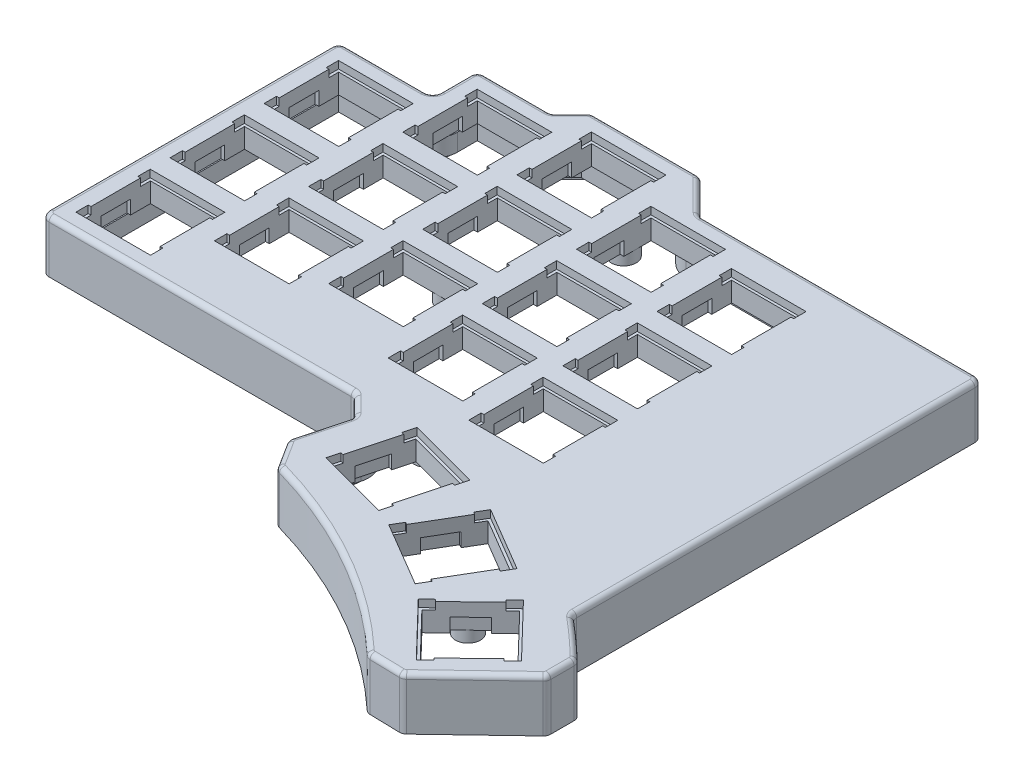
SolidWorks part; units mm, degrees
ref_plane "Piano frontale" through (0, 0, 0) normal (0, 0, 1) x (1, 0, 0)
ref_plane "Piano superiore" through (0, 0, 0) normal (0, 1, 0) x (1, 0, 0)
ref_plane "Piano destro" through (0, 0, 0) normal (1, 0, 0) x (0, 0, -1)
sketch "Schizzo1" plane through (0, 0, 0) normal (0, 1, 0) x (1, 0, 0)
  line L0 (19.05, 28.05) -> (19.05, 9) construction
  line L1 (19.05, 9) -> (19.05, -10.05) construction
  line L2 (38.1, 32.1) -> (38.1, 13.05) construction
  line L3 (38.1, 13.05) -> (38.1, -6) construction
  line L4 (57.15, 25.1) -> (57.15, 6.05) construction
  line L5 (57.15, 6.05) -> (57.15, -13) construction
  line L6 (76.2, 22.35) -> (76.2, 3.3) construction
  line L7 (76.2, 3.3) -> (76.2, -15.75) construction
  line L8 (0, 26.05) -> (0, 30.05) construction
  line L9 (12.05, 35.05) -> (12.05, 39.05) construction
  line L10 (0, 19.05) -> (0, 0) construction
  line L11 (0, 0) -> (0, -19.05) construction
  line L12 (19.05, 22.35) -> (38.1, 22.35) construction
  line L13 (38.1, 22.35) -> (57.15, 22.35) construction
  line L14 (57.15, 22.35) -> (76.2, 22.35) construction
  line L15 (19.05, 22.35) -> (0, 22.35) construction
  line L16 (12.05, 39.05) -> (12.05, 30.05) construction
  line L17 (8.05, 39.05) -> (23.05, 39.05)
  line L18 (23.05, 39.05) -> (27.1, 43.1)
  line L19 (27.1, 43.1) -> (49.1, 43.1)
  line L20 (49.1, 43.1) -> (56.1, 36.1)
  line L21 (56.1, 36.1) -> (113.2, 36.1)
  line L22 (113.2, 36.1) -> (113.2, -46.6839)
  line L23 (-7, -26.05) -> (-7, -30.05) construction
  line L24 (8.05, 39.05) -> (8.05, 30.05)
  line L25 (8.05, 30.05) -> (-11, 30.05)
  line L26 (-11, 30.05) -> (-11, -30.05)
  line L27 (-11, -30.05) -> (52.2495, -30.05)
  line L28 (12.05, 30.05) -> (8.05, 30.05) construction
  line L29 (-7, 19.05) -> (-11, 19.05) construction
  line L30 (45.1, 39.1) -> (45.1, 43.1) construction
  line L31 (31.1, 39.1) -> (27.1, 39.1) construction
  line L32 (27.1, 39.1) -> (27.1, 43.1) construction
  line L33 (45.1, 39.1) -> (49.1, 39.1) construction
  line L34 (49.1, 39.1) -> (49.1, 43.1) construction
  line L35 (57.15, 32.1) -> (57.15, 36.1) construction
  line L36 (27.1, 43.1) -> (27.0899, 42.986) construction
  line L37 (50.1, -113.3763) -> (70.0291, -39) construction
  line L38 (50.1, -113.3763) -> (89.221, -47.0548) construction
  line L39 (50.1, -113.3763) -> (105.5545, -59.9554) construction
  line L40 (52.2495, -49.2894) -> (56.3153, -34.1158)
  line L41 (102.7223, -77.8545) -> (121.3855, -60.0596)
  line L42 (52.2495, -30.05) -> (52.2495, -49.2894)
  line L43 (56.3153, -34.1158) -> (63.57, -36.0597) construction
  line L44 (110.411, -64.9967) -> (113.1713, -67.8917) construction
  line L45 (61.4559, -43.9497) -> (59.2827, -51.1391) construction
  line L46 (56.3153, -34.1158) -> (52.2495, -30.05)
  line L47 (121.3855, -54.0596) -> (121.3855, -60.0596)
  circle A0 centre (50.1, -113.3763) radius 70
  arc A1 (102.7223, -77.8545) -> (52.2495, -49.2894) centre (30.3481, -146.8615) ccw
  arc A2 (121.3855, -54.0596) -> (113.2, -46.6839) centre (30.3481, -146.8615) ccw
  point P0 (19.05, 28.05)
  point P1 (19.05, 9)
  point P2 (19.05, -10.05)
  point P3 (38.1, 32.1)
  point P4 (38.1, 13.05)
  point P5 (38.1, -6)
  point P6 (57.15, 25.1)
  point P7 (57.15, 6.05)
  point P8 (57.15, -13)
  point P9 (76.2, 22.35)
  point P10 (76.2, 3.3)
  point P11 (76.2, -15.75)
  point P23 (0, 19.05)
  point P25 (0, 19.05)
  point P26 (0, -19.05)
  point P43 (76.2, 22.35)
  point P46 (0, 0)
  point P48 (19.05, 28.05)
  point P49 (19.05, 9)
  point P51 (19.05, -10.05)
  point P53 (38.1, 32.1)
  point P54 (38.1, 13.05)
  point P55 (38.1, -6)
  point P59 (57.15, -13)
  point P60 (57.15, 6.05)
  point P61 (57.15, 25.1)
  point P62 (76.2, -15.75)
  point P63 (76.2, 3.3)
  point P69 (50.1, -113.3763)
  point P71 (0, 19.05)
  point P76 (0, -19.05)
  point P80 (105.5545, -59.9554)
  point P86 (89.221, -47.0548)
  point P96 (66.1468, -53.4889)
  line B0 (-7, 26.05) -> (-7, 12.05)
  line B1 (-7, 12.05) -> (7, 12.05)
  line B2 (7, 12.05) -> (7, 26.05)
  line B3 (7, 26.05) -> (-7, 26.05)
  line B4 (0, 26.05) -> (0, 12.05) construction
  line B5 (-7, 19.05) -> (7, 19.05) construction
  line B6 (7.55, 24.075) -> (7.55, 26.575)
  line B7 (-7.55, 26.575) -> (7.55, 26.575)
  line B8 (-7.55, 11.525) -> (7.55, 11.525)
  line B9 (-7, 24.075) -> (-7.55, 24.075)
  line B10 (-7.55, 24.075) -> (-7.55, 26.575)
  line B11 (7, 24.075) -> (7.55, 24.075)
  line B12 (7, 12.05) -> (-7, 12.05)
  line B13 (7, 14.025) -> (7.55, 14.025)
  line B14 (7.55, 14.025) -> (7.55, 11.525)
  line B15 (-7.55, 14.025) -> (-7.55, 11.525)
  line B16 (-7, 14.025) -> (-7.55, 14.025)
  line B17 (-7, 7) -> (-7, -7)
  line B18 (-7, -7) -> (7, -7)
  line B19 (7, -7) -> (7, 7)
  line B20 (7, 7) -> (-7, 7)
  line B21 (0, 7) -> (0, -7) construction
  line B22 (-7, 0) -> (7, 0) construction
  line B23 (7.55, 5.025) -> (7.55, 7.525)
  line B24 (-7.55, 7.525) -> (7.55, 7.525)
  line B25 (-7.55, -7.525) -> (7.55, -7.525)
  line B26 (-7, 5.025) -> (-7.55, 5.025)
  line B27 (-7.55, 5.025) -> (-7.55, 7.525)
  line B28 (7, 5.025) -> (7.55, 5.025)
  line B29 (7, -7) -> (-7, -7)
  line B30 (7, -5.025) -> (7.55, -5.025)
  line B31 (7.55, -5.025) -> (7.55, -7.525)
  line B32 (-7.55, -5.025) -> (-7.55, -7.525)
  line B33 (-7, -5.025) -> (-7.55, -5.025)
  line B34 (12.05, -3.05) -> (12.05, -17.05)
  line B35 (12.05, -17.05) -> (26.05, -17.05)
  line B36 (26.05, -17.05) -> (26.05, -3.05)
  line B37 (26.05, -3.05) -> (12.05, -3.05)
  line B38 (19.05, -3.05) -> (19.05, -17.05) construction
  line B39 (12.05, -10.05) -> (26.05, -10.05) construction
  line B40 (26.6, -5.025) -> (26.6, -2.525)
  line B41 (11.5, -2.525) -> (26.6, -2.525)
  line B42 (11.5, -17.575) -> (26.6, -17.575)
  line B43 (12.05, -5.025) -> (11.5, -5.025)
  line B44 (11.5, -5.025) -> (11.5, -2.525)
  line B45 (26.05, -5.025) -> (26.6, -5.025)
  line B46 (26.05, -17.05) -> (12.05, -17.05)
  line B47 (26.05, -15.075) -> (26.6, -15.075)
  line B48 (26.6, -15.075) -> (26.6, -17.575)
  line B49 (11.5, -15.075) -> (11.5, -17.575)
  line B50 (12.05, -15.075) -> (11.5, -15.075)
  line B51 (12.05, 16) -> (12.05, 2)
  line B52 (12.05, 2) -> (26.05, 2)
  line B53 (26.05, 2) -> (26.05, 16)
  line B54 (26.05, 16) -> (12.05, 16)
  line B55 (19.05, 16) -> (19.05, 2) construction
  line B56 (12.05, 9) -> (26.05, 9) construction
  line B57 (26.6, 14.025) -> (26.6, 16.525)
  line B58 (11.5, 16.525) -> (26.6, 16.525)
  line B59 (11.5, 1.475) -> (26.6, 1.475)
  line B60 (12.05, 14.025) -> (11.5, 14.025)
  line B61 (11.5, 14.025) -> (11.5, 16.525)
  line B62 (26.05, 14.025) -> (26.6, 14.025)
  line B63 (26.05, 2) -> (12.05, 2)
  line B64 (26.05, 3.975) -> (26.6, 3.975)
  line B65 (26.6, 3.975) -> (26.6, 1.475)
  line B66 (11.5, 3.975) -> (11.5, 1.475)
  line B67 (12.05, 3.975) -> (11.5, 3.975)
  line B68 (12.05, 35.05) -> (12.05, 21.05)
  line B69 (12.05, 21.05) -> (26.05, 21.05)
  line B70 (26.05, 21.05) -> (26.05, 35.05)
  line B71 (26.05, 35.05) -> (12.05, 35.05)
  line B72 (19.05, 35.05) -> (19.05, 21.05) construction
  line B73 (12.05, 28.05) -> (26.05, 28.05) construction
  line B74 (26.6, 33.075) -> (26.6, 35.575)
  line B75 (11.5, 35.575) -> (26.6, 35.575)
  line B76 (11.5, 20.525) -> (26.6, 20.525)
  line B77 (12.05, 33.075) -> (11.5, 33.075)
  line B78 (11.5, 33.075) -> (11.5, 35.575)
  line B79 (26.05, 33.075) -> (26.6, 33.075)
  line B80 (26.05, 21.05) -> (12.05, 21.05)
  line B81 (26.05, 23.025) -> (26.6, 23.025)
  line B82 (26.6, 23.025) -> (26.6, 20.525)
  line B83 (11.5, 23.025) -> (11.5, 20.525)
  line B84 (12.05, 23.025) -> (11.5, 23.025)
  line B85 (31.1, 39.1) -> (31.1, 25.1)
  line B86 (31.1, 25.1) -> (45.1, 25.1)
  line B87 (45.1, 25.1) -> (45.1, 39.1)
  line B88 (45.1, 39.1) -> (31.1, 39.1)
  line B89 (38.1, 39.1) -> (38.1, 25.1) construction
  line B90 (31.1, 32.1) -> (45.1, 32.1) construction
  line B91 (45.65, 37.125) -> (45.65, 39.625)
  line B92 (30.55, 39.625) -> (45.65, 39.625)
  line B93 (30.55, 24.575) -> (45.65, 24.575)
  line B94 (31.1, 37.125) -> (30.55, 37.125)
  line B95 (30.55, 37.125) -> (30.55, 39.625)
  line B96 (45.1, 37.125) -> (45.65, 37.125)
  line B97 (45.1, 25.1) -> (31.1, 25.1)
  line B98 (45.1, 27.075) -> (45.65, 27.075)
  line B99 (45.65, 27.075) -> (45.65, 24.575)
  line B100 (30.55, 27.075) -> (30.55, 24.575)
  line B101 (31.1, 27.075) -> (30.55, 27.075)
  line B102 (31.1, 20.05) -> (31.1, 6.05)
  line B103 (31.1, 6.05) -> (45.1, 6.05)
  line B104 (45.1, 6.05) -> (45.1, 20.05)
  line B105 (45.1, 20.05) -> (31.1, 20.05)
  line B106 (38.1, 20.05) -> (38.1, 6.05) construction
  line B107 (31.1, 13.05) -> (45.1, 13.05) construction
  line B108 (45.65, 18.075) -> (45.65, 20.575)
  line B109 (30.55, 20.575) -> (45.65, 20.575)
  line B110 (30.55, 5.525) -> (45.65, 5.525)
  line B111 (31.1, 18.075) -> (30.55, 18.075)
  line B112 (30.55, 18.075) -> (30.55, 20.575)
  line B113 (45.1, 18.075) -> (45.65, 18.075)
  line B114 (45.1, 6.05) -> (31.1, 6.05)
  line B115 (45.1, 8.025) -> (45.65, 8.025)
  line B116 (45.65, 8.025) -> (45.65, 5.525)
  line B117 (30.55, 8.025) -> (30.55, 5.525)
  line B118 (31.1, 8.025) -> (30.55, 8.025)
  line B119 (31.1, 1) -> (31.1, -13)
  line B120 (31.1, -13) -> (45.1, -13)
  line B121 (45.1, -13) -> (45.1, 1)
  line B122 (45.1, 1) -> (31.1, 1)
  line B123 (38.1, 1) -> (38.1, -13) construction
  line B124 (31.1, -6) -> (45.1, -6) construction
  line B125 (45.65, -0.975) -> (45.65, 1.525)
  line B126 (30.55, 1.525) -> (45.65, 1.525)
  line B127 (30.55, -13.525) -> (45.65, -13.525)
  line B128 (31.1, -0.975) -> (30.55, -0.975)
  line B129 (30.55, -0.975) -> (30.55, 1.525)
  line B130 (45.1, -0.975) -> (45.65, -0.975)
  line B131 (45.1, -13) -> (31.1, -13)
  line B132 (45.1, -11.025) -> (45.65, -11.025)
  line B133 (45.65, -11.025) -> (45.65, -13.525)
  line B134 (30.55, -11.025) -> (30.55, -13.525)
  line B135 (31.1, -11.025) -> (30.55, -11.025)
  line B136 (50.15, -6) -> (50.15, -20)
  line B137 (50.15, -20) -> (64.15, -20)
  line B138 (64.15, -20) -> (64.15, -6)
  line B139 (64.15, -6) -> (50.15, -6)
  line B140 (57.15, -6) -> (57.15, -20) construction
  line B141 (50.15, -13) -> (64.15, -13) construction
  line B142 (64.7, -7.975) -> (64.7, -5.475)
  line B143 (49.6, -5.475) -> (64.7, -5.475)
  line B144 (49.6, -20.525) -> (64.7, -20.525)
  line B145 (50.15, -7.975) -> (49.6, -7.975)
  line B146 (49.6, -7.975) -> (49.6, -5.475)
  line B147 (64.15, -7.975) -> (64.7, -7.975)
  line B148 (64.15, -20) -> (50.15, -20)
  line B149 (64.15, -18.025) -> (64.7, -18.025)
  line B150 (64.7, -18.025) -> (64.7, -20.525)
  line B151 (49.6, -18.025) -> (49.6, -20.525)
  line B152 (50.15, -18.025) -> (49.6, -18.025)
  line B153 (50.15, 13.05) -> (50.15, -0.95)
  line B154 (50.15, -0.95) -> (64.15, -0.95)
  line B155 (64.15, -0.95) -> (64.15, 13.05)
  line B156 (64.15, 13.05) -> (50.15, 13.05)
  line B157 (57.15, 13.05) -> (57.15, -0.95) construction
  line B158 (50.15, 6.05) -> (64.15, 6.05) construction
  line B159 (64.7, 11.075) -> (64.7, 13.575)
  line B160 (49.6, 13.575) -> (64.7, 13.575)
  line B161 (49.6, -1.475) -> (64.7, -1.475)
  line B162 (50.15, 11.075) -> (49.6, 11.075)
  line B163 (49.6, 11.075) -> (49.6, 13.575)
  line B164 (64.15, 11.075) -> (64.7, 11.075)
  line B165 (64.15, -0.95) -> (50.15, -0.95)
  line B166 (64.15, 1.025) -> (64.7, 1.025)
  line B167 (64.7, 1.025) -> (64.7, -1.475)
  line B168 (49.6, 1.025) -> (49.6, -1.475)
  line B169 (50.15, 1.025) -> (49.6, 1.025)
  line B170 (50.15, 32.1) -> (50.15, 18.1)
  line B171 (50.15, 18.1) -> (64.15, 18.1)
  line B172 (64.15, 18.1) -> (64.15, 32.1)
  line B173 (64.15, 32.1) -> (50.15, 32.1)
  line B174 (57.15, 32.1) -> (57.15, 18.1) construction
  line B175 (50.15, 25.1) -> (64.15, 25.1) construction
  line B176 (64.7, 30.125) -> (64.7, 32.625)
  line B177 (49.6, 32.625) -> (64.7, 32.625)
  line B178 (49.6, 17.575) -> (64.7, 17.575)
  line B179 (50.15, 30.125) -> (49.6, 30.125)
  line B180 (49.6, 30.125) -> (49.6, 32.625)
  line B181 (64.15, 30.125) -> (64.7, 30.125)
  line B182 (64.15, 18.1) -> (50.15, 18.1)
  line B183 (64.15, 20.075) -> (64.7, 20.075)
  line B184 (64.7, 20.075) -> (64.7, 17.575)
  line B185 (49.6, 20.075) -> (49.6, 17.575)
  line B186 (50.15, 20.075) -> (49.6, 20.075)
  line B187 (69.2, 29.35) -> (69.2, 15.35)
  line B188 (69.2, 15.35) -> (83.2, 15.35)
  line B189 (83.2, 15.35) -> (83.2, 29.35)
  line B190 (83.2, 29.35) -> (69.2, 29.35)
  line B191 (76.2, 29.35) -> (76.2, 15.35) construction
  line B192 (69.2, 22.35) -> (83.2, 22.35) construction
  line B193 (83.75, 27.375) -> (83.75, 29.875)
  line B194 (68.65, 29.875) -> (83.75, 29.875)
  line B195 (68.65, 14.825) -> (83.75, 14.825)
  line B196 (69.2, 27.375) -> (68.65, 27.375)
  line B197 (68.65, 27.375) -> (68.65, 29.875)
  line B198 (83.2, 27.375) -> (83.75, 27.375)
  line B199 (83.2, 15.35) -> (69.2, 15.35)
  line B200 (83.2, 17.325) -> (83.75, 17.325)
  line B201 (83.75, 17.325) -> (83.75, 14.825)
  line B202 (68.65, 17.325) -> (68.65, 14.825)
  line B203 (69.2, 17.325) -> (68.65, 17.325)
  line B204 (69.2, 10.3) -> (69.2, -3.7)
  line B205 (69.2, -3.7) -> (83.2, -3.7)
  line B206 (83.2, -3.7) -> (83.2, 10.3)
  line B207 (83.2, 10.3) -> (69.2, 10.3)
  line B208 (76.2, 10.3) -> (76.2, -3.7) construction
  line B209 (69.2, 3.3) -> (83.2, 3.3) construction
  line B210 (83.75, 8.325) -> (83.75, 10.825)
  line B211 (68.65, 10.825) -> (83.75, 10.825)
  line B212 (68.65, -4.225) -> (83.75, -4.225)
  line B213 (69.2, 8.325) -> (68.65, 8.325)
  line B214 (68.65, 8.325) -> (68.65, 10.825)
  line B215 (83.2, 8.325) -> (83.75, 8.325)
  line B216 (83.2, -3.7) -> (69.2, -3.7)
  line B217 (83.2, -1.725) -> (83.75, -1.725)
  line B218 (83.75, -1.725) -> (83.75, -4.225)
  line B219 (68.65, -1.725) -> (68.65, -4.225)
  line B220 (69.2, -1.725) -> (68.65, -1.725)
  line B221 (69.2, -8.75) -> (69.2, -22.75)
  line B222 (69.2, -22.75) -> (83.2, -22.75)
  line B223 (83.2, -22.75) -> (83.2, -8.75)
  line B224 (83.2, -8.75) -> (69.2, -8.75)
  line B225 (76.2, -8.75) -> (76.2, -22.75) construction
  line B226 (69.2, -15.75) -> (83.2, -15.75) construction
  line B227 (83.75, -10.725) -> (83.75, -8.225)
  line B228 (68.65, -8.225) -> (83.75, -8.225)
  line B229 (68.65, -23.275) -> (83.75, -23.275)
  line B230 (69.2, -10.725) -> (68.65, -10.725)
  line B231 (68.65, -10.725) -> (68.65, -8.225)
  line B232 (83.2, -10.725) -> (83.75, -10.725)
  line B233 (83.2, -22.75) -> (69.2, -22.75)
  line B234 (83.2, -20.775) -> (83.75, -20.775)
  line B235 (83.75, -20.775) -> (83.75, -23.275)
  line B236 (68.65, -20.775) -> (68.65, -23.275)
  line B237 (69.2, -20.775) -> (68.65, -20.775)
  line B238 (-7, -12.05) -> (-7, -26.05)
  line B239 (-7, -26.05) -> (7, -26.05)
  line B240 (7, -26.05) -> (7, -12.05)
  line B241 (7, -12.05) -> (-7, -12.05)
  line B242 (0, -12.05) -> (0, -26.05) construction
  line B243 (-7, -19.05) -> (7, -19.05) construction
  line B244 (7.55, -14.025) -> (7.55, -11.525)
  line B245 (-7.55, -11.525) -> (7.55, -11.525)
  line B246 (-7.55, -26.575) -> (7.55, -26.575)
  line B247 (-7, -14.025) -> (-7.55, -14.025)
  line B248 (-7.55, -14.025) -> (-7.55, -11.525)
  line B249 (7, -14.025) -> (7.55, -14.025)
  line B250 (7, -26.05) -> (-7, -26.05)
  line B251 (7, -24.075) -> (7.55, -24.075)
  line B252 (7.55, -24.075) -> (7.55, -26.575)
  line B253 (-7.55, -24.075) -> (-7.55, -26.575)
  line B254 (-7, -24.075) -> (-7.55, -24.075)
  line B255 (65.0793, -30.4268) -> (61.4559, -43.9497)
  line B256 (61.4559, -43.9497) -> (74.9788, -47.5732)
  line B257 (74.9788, -47.5732) -> (78.6023, -34.0503)
  line B258 (78.6023, -34.0503) -> (65.0793, -30.4268)
  line B259 (71.8408, -32.2385) -> (68.2173, -45.7615) construction
  line B260 (63.2676, -37.1883) -> (76.7905, -40.8117) construction
  line B261 (78.6224, -36.1003) -> (79.2694, -33.6855)
  line B262 (64.6839, -29.7773) -> (79.2694, -33.6855)
  line B263 (60.7887, -44.3145) -> (75.3742, -48.2227)
  line B264 (64.5682, -32.3345) -> (64.0369, -32.1921)
  line B265 (64.0369, -32.1921) -> (64.6839, -29.7773)
  line B266 (78.0911, -35.958) -> (78.6224, -36.1003)
  line B267 (74.9788, -47.5732) -> (61.4559, -43.9497)
  line B268 (75.49, -45.6655) -> (76.0212, -45.8079)
  line B269 (76.0212, -45.8079) -> (75.3742, -48.2227)
  line B270 (61.4358, -41.8997) -> (60.7887, -44.3145)
  line B271 (61.967, -42.042) -> (61.4358, -41.8997)
  line B272 (86.7482, -37.4691) -> (79.6353, -49.5275)
  line B273 (79.6353, -49.5275) -> (91.6938, -56.6404)
  line B274 (91.6938, -56.6404) -> (98.8067, -44.582)
  line B275 (98.8067, -44.582) -> (86.7482, -37.4691)
  line B276 (92.7775, -41.0255) -> (85.6646, -53.084) construction
  line B277 (83.1918, -43.4983) -> (95.2502, -50.6112) construction
  line B278 (98.277, -46.5625) -> (99.5472, -44.4092)
  line B279 (86.5413, -36.7374) -> (99.5472, -44.4092)
  line B280 (78.8949, -49.7003) -> (91.9008, -57.3721)
  line B281 (85.7448, -39.1702) -> (85.2711, -38.8907)
  line B282 (85.2711, -38.8907) -> (86.5413, -36.7374)
  line B283 (97.8033, -46.2831) -> (98.277, -46.5625)
  line B284 (91.6938, -56.6404) -> (79.6353, -49.5275)
  line B285 (92.6972, -54.9393) -> (93.1709, -55.2188)
  line B286 (93.1709, -55.2188) -> (91.9008, -57.3721)
  line B287 (80.165, -47.547) -> (78.8949, -49.7003)
  line B288 (80.6388, -47.8264) -> (80.165, -47.547)
  line B289 (105.7394, -50.0576) -> (95.6568, -59.7705)
  line B290 (95.6568, -59.7705) -> (105.3697, -69.8531)
  line B291 (105.3697, -69.8531) -> (115.4523, -60.1403)
  line B292 (115.4523, -60.1403) -> (105.7394, -50.0576)
  line B293 (110.5959, -55.0989) -> (100.5132, -64.8118) construction
  line B294 (100.6981, -54.9141) -> (110.411, -64.9967) construction
  line B295 (114.4115, -61.9066) -> (116.212, -60.1721)
  line B296 (105.7359, -49.2973) -> (116.212, -60.1721)
  line B297 (94.8971, -59.7386) -> (105.3731, -70.6135)
  line B298 (104.317, -51.4278) -> (103.9355, -51.0317)
  line B299 (103.9355, -51.0317) -> (105.7359, -49.2973)
  line B300 (114.0299, -61.5105) -> (114.4115, -61.9066)
  line B301 (105.3697, -69.8531) -> (95.6568, -59.7705)
  line B302 (106.792, -68.4829) -> (107.1736, -68.879)
  line B303 (107.1736, -68.879) -> (105.3731, -70.6135)
  line B304 (96.6976, -58.0042) -> (94.8971, -59.7386)
  line B305 (97.0791, -58.4003) -> (96.6976, -58.0042)
  dimension "D17" = 140
  dimension "D21" = 130
  dimension "D18" = 100
  dimension "D2" = 19.05
  dimension "D5" = 2.75
  dimension "D6" = 7
  dimension "D3" = 9
  dimension "D13" = 19.05
  dimension "D7" = 4
  dimension "D8" = 30
  dimension "D4" = 4.05
  dimension "D9" = 45
  dimension "D10" = 45
  dimension "D14" = 5.05
  dimension "D15" = 5.05
  dimension "D16" = 15
  dimension "D19" = 8
  dimension "D20" = 45
  dimension "D22" = 6
  dimension "D11" = 107.3763
  dimension "D12" = 12
sketch_block_instance "Blocco1-2"
sketch_block "Blocco1" parameters "D1"=14, "D2"=14, "D3"=3.1519, "D4"=2.9137, "D5"=15.1
sketch_block_instance "Blocco1-4"
sketch_block_instance "Blocco1-5"
sketch_block_instance "Blocco1-6"
sketch_block_instance "Blocco1-7"
sketch_block_instance "Blocco1-8"
sketch_block_instance "Blocco1-9"
sketch_block_instance "Blocco1-10"
sketch_block_instance "Blocco1-11"
sketch_block_instance "Blocco1-12"
sketch_block_instance "Blocco1-13"
sketch_block_instance "Blocco1-14"
sketch_block_instance "Blocco1-15"
sketch_block_instance "Blocco1-16"
sketch_block_instance "Blocco1-17"
sketch_block_instance "Blocco1-19"
sketch_block_instance "Blocco1-20"
sketch_block_instance "Blocco1-21" parameters "D14"=15.0314, "D16"=0, "D17"=146.9227, "D18"=401.5251, "D19"=350, "D22"=321.5119, "D21"=134.4226, "D1"=15.2216, "D2"=19.7606, "D3"=19.05, "D4"=3.5682, "D5"=15.1768, "D6"=3.9954, "D7"=7.4894, "D8"=8.3056, "D9"=14, "D10"=7.4056, "D11"=6.4642, "D12"=7.9906, "D13"=37.7892, "D15"=17.4954, "D20"=24.1603, "D23"=17.6251, "D24"=12.8905
extrude "Estrusione-Estrusione3" add sketch "Schizzo1" against normal blind 5.5 contours B292 B291 B290 A0 L41 L47 A2 L22 L21 L20 L19 L18 L17 L24 L25 L26 L27 L46 L40 B256 B255 B258 B257 B273 B272 B275 B274 B289 B241 B240 B239 B238 B224 B223 | A1 L41 A0 L40 | B2 B11 B6 B7 B10 B9 B0 B3 | B0 B16 B15 B8 B14 B13 B2 B1 | B19 B28 B23 B24 B27 B26 B17 B20 | B51 B67 B66 B59 B65 B64 B53 B52 | B53 B62 B57 B58 B61 B60 B51 B54 | B68 B84 B83 B76 B82 B81 B70 B69 | B70 B79 B74 B75 B78 B77 B68 B71 | B87 B96 B91 B92 B95 B94 B85 B88 | B85 B101 B100 B93 B99 B98 B87 B86 | B104 B113 B108 B109 B112 B111 B102 B105 | B102 B118 B117 B110 B116 B115 B104 B103 | B121 B130 B125 B126 B129 B128 B119 B122 | B119 B135 B134 B127 B133 B132 B121 B120 | B36 B45 B40 B41 B44 B43 B34 B37 | B34 B50 B49 B42 B48 B47 B36 B35 | B240 B249 B244 B245 B248 B247 B238 B241 | B17 B33 B32 B25 B31 B30 B19 B18 | B238 B254 B253 B246 B252 B251 B240 B239 | B136 B152 B151 B144 B150 B149 B138 B137 | B138 B147 B142 B143 B146 B145 B136 B139 | B221 B237 B236 B229 B235 B234 B223 B222 | B223 B232 B227 B228 B231 B230 B221 B224 | B204 B220 B219 B212 B218 B217 B206 B205 | B206 B215 B210 B211 B214 B213 B204 B207 | B187 B203 B202 B195 B201 B200 B189 B188 | B189 B198 B193 B194 B197 B196 B187 B190 | B172 B181 B176 B177 B180 B179 B170 B173 | B170 B186 B185 B178 B184 B183 B172 B171 | B155 B164 B159 B160 B163 B162 B153 B156 | B153 B169 B168 B161 B167 B166 B155 B154 | B269 B268 B257 B256 A0 | A0 B270 B263 B269 | B255 B271 B270 A0 B256 | B257 B266 B261 B262 B265 B264 B255 B258 | B274 B283 B278 B279 B282 B281 B272 B275 | B286 B285 B274 B273 A0 | A0 B287 B280 B286 | B272 B288 B287 A0 B273 | B289 B305 B304 A0 B290 | A0 B304 B297 B303 | B303 B302 B291 B290 A0 | B291 B300 B295 B296 B299 B298 B289 B292 region at (65.1419, 0, 4.9179) region at (81.2376, 0, 57.7843) region at (61.2079, 0, 43.0724) region at (68.1367, 0, 46.0623) region at (71.5769, 0, 46.7463) region at (100.2889, 0, 65.0279) region at (103.1289, 0, 67.548) region at (97.8766, 0, 62.0958) region at (79.6345, 0, 48.6176) region at (85.5063, 0, 53.3522) region at (64.3452, 0, 32.104) region at (88.6355, 0, 54.9362) region at (114.8632, 0, 60.9521) region at (85.596, 0, 38.8812) region at (-7.1531, 0, -25.0625) region at (-7.1531, 0, -13.0375) region at (-7.1531, 0, -6.0125) region at (-7.1531, 0, 6.0125) region at (11.8969, 0, 4.0375) region at (11.8969, 0, 16.0625) region at (11.8969, 0, -15.0125) region at (11.8969, 0, -2.9875) region at (11.8969, 0, -34.0625) region at (11.8969, 0, -22.0375) region at (30.9469, 0, -38.1125) region at (30.9469, 0, -26.0875) region at (30.9469, 0, -19.0625) region at (30.9469, 0, -7.0375) region at (30.9469, 0, -0.0125) region at (30.9469, 0, 12.0125) region at (49.9969, 0, 6.9875) region at (49.9969, 0, 19.0125) region at (49.9969, 0, -12.0625) region at (49.9969, 0, -0.0375) region at (49.9969, 0, -31.1125) region at (49.9969, 0, -19.0875) region at (69.0469, 0, -28.3625) region at (69.0469, 0, -16.3375) region at (69.0469, 0, -9.3125) region at (69.0469, 0, 2.7125) region at (69.0469, 0, 9.7375) region at (69.0469, 0, 21.7625) region at (-7.1531, 0, 13.0375) region at (-7.1531, 0, 25.0625)
chamfer "Smusso1" distance 5 angle 45 2 edges at (102.7223, -2.75, 77.8545) (52.2495, -2.75, 49.2894) first distance on face at (78.5441, -2.75, 61.7023)
fillet "Raccordo1" radius 1.5 18 edges at (113.2, -2.75, 46.6839) (121.3855, -2.75, 54.0596) (121.3855, -2.75, 60.0596) (106.341, -2.75, 74.4041) (99.0857, -2.75, 74.2314) (57.2279, -2.75, 50.5419) (53.4937, -2.75, 44.6462) (56.3153, -2.75, 34.1158) (52.2495, -2.75, 30.05) (8.05, -2.75, -30.05) (23.05, -2.75, -39.05) (56.1, -2.75, -36.1) (49.1, -2.75, -43.1) (27.1, -2.75, -43.1) (8.05, -2.75, -39.05) (-11, -2.75, -30.05) (-11, -2.75, 30.05) (113.2, -2.75, -36.1)
sketch "Schizzo2" plane through (0, -5.5, 0) normal (0, -1, 0) x (1, 0, 0)
  line L0 (51.6282, 26.55) -> (-7.5, 26.55)
  line L1 (-7.5, 26.55) -> (-7.5, -26.55)
  line L2 (-7.5, -26.55) -> (6.55, -26.55)
  line L3 (11.55, -31.55) -> (11.55, -35.55)
  line L4 (11.55, -35.55) -> (22.4287, -35.55)
  line L5 (25.9642, -37.0145) -> (28.5497, -39.6)
  line L6 (28.5497, -39.6) -> (47.6503, -39.6)
  line L7 (47.6503, -39.6) -> (53.1858, -34.0645)
  line L8 (56.7213, -32.6) -> (109.7, -32.6)
  line L9 (56.7213, -32.6) -> (106.7503, -32.6) construction
  line L10 (109.7, -32.6) -> (109.7, 45.9804)
  line L11 (117.8855, 55.5409) -> (117.8855, 58.5608)
  line L12 (117.8855, 58.5608) -> (104.975, 70.8706)
  line L13 (104.975, 70.8706) -> (100.5009, 70.7641)
  line L14 (59.4718, 47.5436) -> (57.2716, 44.0698)
  line L15 (57.2716, 44.0698) -> (59.4719, 35.8581)
  line L16 (58.1778, 31.0285) -> (55.1638, 28.0145)
  line L17 (121.3855, 54.6916) -> (121.3855, 59.4173)
  line L18 (120.9206, 60.5029) -> (106.7907, 73.9754)
  line L19 (105.7199, 74.3894) -> (99.6597, 74.245)
  line L20 (56.9206, 50.0568) -> (53.8456, 45.2017)
  line L21 (53.6639, 44.0109) -> (56.0912, 34.9523)
  line L22 (55.7029, 33.5034) -> (52.6889, 30.4893)
  line L23 (51.6282, 30.05) -> (-9.5, 30.05)
  line L24 (-11, 28.55) -> (-11, -28.55)
  line L25 (-9.5, -30.05) -> (6.55, -30.05)
  line L26 (8.05, -31.55) -> (8.05, -37.55)
  line L27 (9.55, -39.05) -> (22.4287, -39.05)
  line L28 (23.4893, -39.4893) -> (26.6607, -42.6607)
  line L29 (27.7213, -43.1) -> (48.4787, -43.1)
  line L30 (49.5393, -42.6607) -> (55.6607, -36.5393)
  line L31 (56.7213, -36.1) -> (111.7, -36.1)
  line L32 (109.7, -29.6503) -> (109.7, 45.9804) construction
  line L33 (113.2, -34.6) -> (113.2, 45.9804)
  line L34 (121.3855, 54.6916) -> (121.3855, 59.4173)
  line L35 (120.9206, 60.5029) -> (106.7907, 73.9754)
  line L36 (105.7199, 74.3894) -> (99.6597, 74.245)
  line L37 (56.9206, 50.0568) -> (53.8456, 45.2017)
  line L38 (53.6639, 44.0109) -> (56.0912, 34.9523)
  line L39 (55.7029, 33.5034) -> (52.6889, 30.4893)
  line L40 (51.6282, 30.05) -> (-9.5, 30.05)
  line L41 (-11, 28.55) -> (-11, -28.55)
  line L42 (-9.5, -30.05) -> (6.55, -30.05)
  line L43 (8.05, -31.55) -> (8.05, -37.55)
  line L44 (9.55, -39.05) -> (22.4287, -39.05)
  line L45 (23.4893, -39.4893) -> (26.6607, -42.6607)
  line L46 (27.7213, -43.1) -> (48.4787, -43.1)
  line L47 (49.5393, -42.6607) -> (55.6607, -36.5393)
  line L48 (56.7213, -36.1) -> (111.7, -36.1)
  line L50 (113.2, -34.6) -> (113.2, 45.9804)
  line L68 (108.6393, -35.6607) -> (112.7607, -31.5393) construction
  line L69 (106.7503, -32.6) -> (109.7, -29.6503) construction
  arc A0 (-7.5, 26.55) -> (-7.5, 26.55) centre (-7.5, 26.55) ccw
  arc A1 (-7.5, -26.55) -> (-7.5, -26.55) centre (-7.5, -26.55) ccw
  arc A2 (11.55, -31.55) -> (6.55, -26.55) centre (6.55, -31.55) ccw
  arc A3 (11.55, -35.55) -> (11.55, -35.55) centre (11.55, -35.55) ccw
  arc A4 (25.9642, -37.0145) -> (22.4287, -35.55) centre (22.4287, -40.55) ccw
  arc A5 (28.5497, -39.6) -> (28.5497, -39.6) centre (28.5497, -39.6) ccw
  arc A6 (47.6503, -39.6) -> (47.6503, -39.6) centre (47.6503, -39.6) ccw
  arc A7 (56.7213, -32.6) -> (53.1858, -34.0645) centre (56.7213, -37.6) ccw
  arc A10 (111.4927, 49.8162) -> (109.7, 45.9804) centre (114.7, 45.9804) ccw
  arc A11 (111.4927, 49.8162) -> (117.8855, 55.5409) centre (30.3481, 146.8615) ccw
  arc A12 (117.8855, 55.5409) -> (117.8855, 55.5409) centre (117.8855, 55.5409) ccw
  arc A13 (117.8855, 58.5608) -> (117.8855, 58.5608) centre (117.8855, 58.5608) ccw
  arc A14 (104.975, 70.8706) -> (104.975, 70.8706) centre (104.975, 70.8706) ccw
  arc A15 (100.5009, 70.7641) -> (100.5009, 70.7641) centre (100.5009, 70.7641) ccw
  arc A16 (59.4718, 47.5436) -> (100.5009, 70.7641) centre (30.3481, 146.8615) ccw
  arc A17 (59.4718, 47.5436) -> (59.4718, 47.5436) centre (59.4718, 47.5436) ccw
  arc A18 (57.2716, 44.0698) -> (57.2716, 44.0698) centre (57.2716, 44.0698) ccw
  arc A19 (58.1778, 31.0285) -> (59.4719, 35.8581) centre (54.6423, 34.564) ccw
  arc A20 (51.6282, 26.55) -> (55.1638, 28.0145) centre (51.6282, 31.55) ccw
  arc A21 (113.7378, 47.1311) -> (120.9307, 53.6156) centre (30.3481, 146.8615) ccw
  arc A22 (120.9307, 53.6156) -> (121.3855, 54.6916) centre (119.8855, 54.6916) ccw
  arc A23 (121.3855, 59.4173) -> (120.9206, 60.5029) centre (119.8855, 59.4173) ccw
  arc A24 (106.7907, 73.9754) -> (105.7199, 74.3894) centre (105.7556, 72.8898) ccw
  arc A25 (99.6597, 74.245) -> (98.6706, 73.8408) centre (99.6954, 72.7454) ccw
  arc A26 (57.7764, 50.6966) -> (98.6706, 73.8408) centre (30.3481, 146.8615) ccw
  arc A27 (57.7764, 50.6966) -> (56.9206, 50.0568) centre (58.1878, 49.2542) ccw
  arc A28 (53.8456, 45.2017) -> (53.6639, 44.0109) centre (55.1128, 44.3991) ccw
  arc A29 (55.7029, 33.5034) -> (56.0912, 34.9523) centre (54.6423, 34.564) ccw
  arc A30 (51.6282, 30.05) -> (52.6889, 30.4893) centre (51.6282, 31.55) ccw
  arc A31 (-9.5, 30.05) -> (-11, 28.55) centre (-9.5, 28.55) ccw
  arc A32 (-11, -28.55) -> (-9.5, -30.05) centre (-9.5, -28.55) ccw
  arc A33 (8.05, -31.55) -> (6.55, -30.05) centre (6.55, -31.55) ccw
  arc A34 (8.05, -37.55) -> (9.55, -39.05) centre (9.55, -37.55) ccw
  arc A35 (23.4893, -39.4893) -> (22.4287, -39.05) centre (22.4287, -40.55) ccw
  arc A36 (26.6607, -42.6607) -> (27.7213, -43.1) centre (27.7213, -41.6) ccw
  arc A37 (48.4787, -43.1) -> (49.5393, -42.6607) centre (48.4787, -41.6) ccw
  arc A38 (56.7213, -36.1) -> (55.6607, -36.5393) centre (56.7213, -37.6) ccw
  arc A41 (113.7378, 47.1311) -> (113.2, 45.9804) centre (114.7, 45.9804) ccw
  arc A42 (113.7378, 47.1311) -> (120.9307, 53.6156) centre (30.3481, 146.8615) ccw
  arc A43 (120.9307, 53.6156) -> (121.3855, 54.6916) centre (119.8855, 54.6916) ccw
  arc A44 (121.3855, 59.4173) -> (120.9206, 60.5029) centre (119.8855, 59.4173) ccw
  arc A45 (106.7907, 73.9754) -> (105.7199, 74.3894) centre (105.7556, 72.8898) ccw
  arc A46 (99.6597, 74.245) -> (98.6706, 73.8408) centre (99.6954, 72.7454) ccw
  arc A47 (57.7764, 50.6966) -> (98.6706, 73.8408) centre (30.3481, 146.8615) ccw
  arc A48 (57.7764, 50.6966) -> (56.9206, 50.0568) centre (58.1878, 49.2542) ccw
  arc A49 (53.8456, 45.2017) -> (53.6639, 44.0109) centre (55.1128, 44.3991) ccw
  arc A50 (55.7029, 33.5034) -> (56.0912, 34.9523) centre (54.6423, 34.564) ccw
  arc A51 (51.6282, 30.05) -> (52.6889, 30.4893) centre (51.6282, 31.55) ccw
  arc A52 (-9.5, 30.05) -> (-11, 28.55) centre (-9.5, 28.55) ccw
  arc A53 (-11, -28.55) -> (-9.5, -30.05) centre (-9.5, -28.55) ccw
  arc A54 (8.05, -31.55) -> (6.55, -30.05) centre (6.55, -31.55) ccw
  arc A55 (8.05, -37.55) -> (9.55, -39.05) centre (9.55, -37.55) ccw
  arc A56 (23.4893, -39.4893) -> (22.4287, -39.05) centre (22.4287, -40.55) ccw
  arc A57 (26.6607, -42.6607) -> (27.7213, -43.1) centre (27.7213, -41.6) ccw
  arc A58 (48.4787, -43.1) -> (49.5393, -42.6607) centre (48.4787, -41.6) ccw
  arc A59 (56.7213, -36.1) -> (55.6607, -36.5393) centre (56.7213, -37.6) ccw
  arc A62 (113.7378, 47.1311) -> (113.2, 45.9804) centre (114.7, 45.9804) ccw
  arc A79 (111.7, -36.1) -> (113.2, -34.6) centre (111.7, -34.6) ccw
  arc A80 (111.7, -36.1) -> (113.2, -34.6) centre (111.7, -34.6) ccw
  arc A84 (113.2, -36.1) -> (108.6393, -35.6607) centre (110.6461, -38.7203) ccw construction
  arc A85 (112.7607, -31.5393) -> (113.2, -36.1) centre (115.8203, -33.5461) ccw construction
  arc A86 (106.7503, -32.6) -> (106.7503, -32.6) centre (106.7503, -32.6) ccw construction
  arc A87 (109.7, -29.6503) -> (109.7, -29.6503) centre (109.7, -29.6503) ccw construction
  point P119 (0, 0)
  point P120 (0, 0)
  point P121 (109.7, -29.6503)
  point P122 (110.9492, -32.6)
  point P124 (113.2, -32.6)
  point P125 (113.2, -32.6)
  point P127 (110.9492, -32.6)
  dimension "D1" = 0
  dimension "D2" = 3.5
extrude "Estrusione-Estrusione4" add sketch "Schizzo2" along normal offset from surface (2.8972 mm away) 10.6 up to face at (105.5545, 0, 59.9554)
sketch "Schizzo4" plane through (0, -5.5, 0) normal (0, -1, 0) x (-1, 0, 0)
  line L0 (-69.2, -22.75) -> (-56.6708, -29.5215) construction
  line L4 (-12.05, 23.05) -> (-7, 23.05) construction
  line L5 (-12.05, 35.05) -> (-12.05, 21.05) construction
  line L6 (-7, 12.05) -> (-7, 26.05) construction
  line L7 (-50.15, 29.1) -> (-45.1, 29.1) construction
  line L8 (-50.15, 32.1) -> (-50.15, 18.1) construction
  line L9 (-45.1, 25.1) -> (-45.1, 39.1) construction
  line L12 (-80.2, 10.3) -> (-80.2, 15.35) construction
  line L13 (-83.2, 10.3) -> (-69.2, 10.3) construction
  line L14 (-69.2, 15.35) -> (-83.2, 15.35) construction
  line L15 (-7, 26.05) -> (7, 26.05) construction
  line L16 (-64.15, 32.1) -> (-50.15, 32.1) construction
  line L17 (-83.2, -3.7) -> (-83.2, 10.3) construction
  line L18 (-51.6282, -26.55) -> (7.5, -26.55) construction
  line L19 (-7, -26.05) -> (-7, -12.05) construction
  line L20 (-55.1638, -28.0145) -> (-58.1778, -31.0285) construction
  line L21 (-95.2502, -50.6112) -> (-100.6981, -54.9141) construction
  line L22 (-91.6938, -56.6404) -> (-98.8067, -44.582) construction
  line L23 (-105.7394, -50.0576) -> (-95.6568, -59.7705) construction
  line L24 (-38.1, 6.05) -> (-38.1, 1) construction
  line L25 (-31.1, 6.05) -> (-45.1, 6.05) construction
  line L26 (-45.1, 1) -> (-31.1, 1) construction
  circle A0 centre (-38.1, 3.525) radius 0.6
  circle A1 centre (-9.525, 23.05) radius 0.6
  circle A2 centre (-47.625, 29.1) radius 0.6
  circle A3 centre (-80.2, 12.825) radius 0.6
  circle A4 centre (-97.9742, -52.7626) radius 2.525
  circle A5 centre (-10, -22.05) radius 0.6
  circle A6 centre (-62.9354, -26.1357) radius 0.6
  circle A7 centre (-62.9354, -26.1357) radius 2.525
  circle A8 centre (-97.9742, -52.7626) radius 0.6
  circle A9 centre (-80.2, 12.825) radius 2.525
  circle A10 centre (-47.625, 29.1) radius 2.525
  circle A11 centre (-38.1, 3.525) radius 2.525
  circle A12 centre (-9.525, 23.05) radius 2.525
  circle A13 centre (-10, -22.05) radius 2.525
  dimension "D1" = 3
  dimension "D4" = 4.5
  dimension "D6" = 1.2
  dimension "D2" = 3
  dimension "D3" = 3
  dimension "D5" = 3
sketch "Schizzo5" plane through (0, -10.6, 0) normal (0, -1, 0) x (1, 0, 0)
  line L2 (55.3287, 44.3662) -> (57.7332, 35.3923)
  line L3 (58.316, 49.0828) -> (55.3287, 44.3662)
  line L4 (56.905, 32.3013) -> (53.891, 29.2873)
  line L5 (105.6775, 72.6879) -> (99.7764, 72.5473)
  line L6 (119.6855, 59.3316) -> (105.6775, 72.6879)
  line L7 (119.6855, 54.7761) -> (119.6855, 59.3316)
  line L8 (111.5, -30.3958) -> (111.5, 45.9804)
  line L9 (107.4958, -34.4) -> (111.5, -30.3958)
  line L10 (56.7213, -34.4) -> (107.4958, -34.4)
  line L11 (48.3958, -41.4) -> (54.4586, -35.3373)
  line L13 (27.8042, -41.4) -> (48.3958, -41.4)
  line L14 (24.6914, -38.2873) -> (27.8042, -41.4)
  line L15 (9.75, -37.35) -> (22.4287, -37.35)
  line L16 (9.75, -31.55) -> (9.75, -37.35)
  line L17 (121.3855, 54.6916) -> (121.3855, 59.4173)
  line L18 (120.9206, 60.5029) -> (106.7907, 73.9754)
  line L19 (105.7199, 74.3894) -> (99.6597, 74.245)
  line L20 (56.9206, 50.0568) -> (53.8456, 45.2017)
  line L21 (53.6639, 44.0109) -> (56.0912, 34.9523)
  line L22 (55.7029, 33.5034) -> (52.6889, 30.4893)
  line L23 (51.6282, 30.05) -> (-9.5, 30.05)
  line L24 (-11, 28.55) -> (-11, -28.55)
  line L25 (-9.5, -30.05) -> (6.55, -30.05)
  line L26 (8.05, -31.55) -> (8.05, -37.55)
  line L27 (9.55, -39.05) -> (22.4287, -39.05)
  line L28 (23.4893, -39.4893) -> (26.6607, -42.6607)
  line L29 (27.7213, -43.1) -> (48.4787, -43.1)
  line L30 (49.5393, -42.6607) -> (55.6607, -36.5393)
  line L31 (56.7213, -36.1) -> (111.7, -36.1)
  line L33 (113.2, -34.6) -> (113.2, 45.9804)
  line L34 (121.3855, 54.6916) -> (121.3855, 59.4173)
  line L35 (120.9206, 60.5029) -> (106.7907, 73.9754)
  line L36 (105.7199, 74.3894) -> (99.6597, 74.245)
  line L37 (56.9206, 50.0568) -> (53.8456, 45.2017)
  line L38 (53.6639, 44.0109) -> (56.0912, 34.9523)
  line L39 (55.7029, 33.5034) -> (52.6889, 30.4893)
  line L40 (51.6282, 30.05) -> (-9.5, 30.05)
  line L41 (-11, 28.55) -> (-11, -28.55)
  line L42 (-9.5, -30.05) -> (6.55, -30.05)
  line L43 (8.05, -31.55) -> (8.05, -37.55)
  line L44 (9.55, -39.05) -> (22.4287, -39.05)
  line L45 (23.4893, -39.4893) -> (26.6607, -42.6607)
  line L46 (27.7213, -43.1) -> (48.4787, -43.1)
  line L47 (49.5393, -42.6607) -> (55.6607, -36.5393)
  line L48 (56.7213, -36.1) -> (111.7, -36.1)
  line L50 (113.2, -34.6) -> (113.2, 45.9804)
  line L51 (-9.2, -28.35) -> (6.55, -28.35)
  line L53 (111.5, 28.35) -> (-9.2, 28.35)
  line L54 (-9.2, -26.55) -> (-9.2, 26.55)
  line L55 (-9.2, -28.35) -> (-9.2, 28.35)
  line L56 (9.75, -31.55) -> (9.75, -37.55) construction
  line L57 (9.55, -37.35) -> (22.4287, -37.35) construction
  line L58 (24.6914, -38.2873) -> (27.8627, -41.4586) construction
  line L59 (27.7213, -41.4) -> (48.4787, -41.4) construction
  line L60 (48.3373, -41.4586) -> (54.4586, -35.3373) construction
  line L61 (56.7213, -34.4) -> (111.7, -34.4) construction
  line L63 (111.5, -34.6) -> (111.5, 45.9804) construction
  line L64 (119.6855, 54.6916) -> (119.6855, 59.4173) construction
  line L65 (119.7475, 59.2725) -> (105.6176, 72.745) construction
  line L66 (105.7603, 72.6898) -> (99.7002, 72.5455) construction
  line L67 (58.3568, 49.1472) -> (55.2818, 44.2921) construction
  line L68 (55.306, 44.4509) -> (57.7332, 35.3923) construction
  line L69 (51.6282, 28.35) -> (-9.5, 28.35) construction
  line L70 (-9.5, -28.35) -> (6.55, -28.35) construction
  arc A0 (51.6282, 28.35) -> (53.891, 29.2873) centre (51.6282, 31.55) ccw
  arc A1 (56.905, 32.3013) -> (57.7332, 35.3923) centre (54.6423, 34.564) ccw
  arc A2 (58.316, 49.0828) -> (99.7764, 72.5473) centre (30.3481, 146.8615) ccw
  arc A3 (112.6473, 48.4353) -> (119.6855, 54.7761) centre (30.3481, 146.8615) ccw
  arc A4 (112.6473, 48.4353) -> (111.5, 45.9804) centre (114.7, 45.9804) ccw
  arc A5 (56.7213, -34.4) -> (54.4586, -35.3373) centre (56.7213, -37.6) ccw
  arc A6 (24.6914, -38.2873) -> (22.4287, -37.35) centre (22.4287, -40.55) ccw
  arc A7 (9.75, -31.55) -> (6.55, -28.35) centre (6.55, -31.55) ccw
  arc A8 (112.6473, 48.4353) -> (119.7461, 54.835) centre (30.3481, 146.8615) ccw construction
  arc A9 (58.2427, 49.0618) -> (99.8321, 72.5994) centre (30.3481, 146.8615) ccw construction
  arc A21 (113.7378, 47.1311) -> (120.9307, 53.6156) centre (30.3481, 146.8615) ccw
  arc A22 (120.9307, 53.6156) -> (121.3855, 54.6916) centre (119.8855, 54.6916) ccw
  arc A23 (121.3855, 59.4173) -> (120.9206, 60.5029) centre (119.8855, 59.4173) ccw
  arc A24 (106.7907, 73.9754) -> (105.7199, 74.3894) centre (105.7556, 72.8898) ccw
  arc A25 (99.6597, 74.245) -> (98.6706, 73.8408) centre (99.6954, 72.7454) ccw
  arc A26 (57.7764, 50.6966) -> (98.6706, 73.8408) centre (30.3481, 146.8615) ccw
  arc A27 (57.7764, 50.6966) -> (56.9206, 50.0568) centre (58.1878, 49.2542) ccw
  arc A28 (53.8456, 45.2017) -> (53.6639, 44.0109) centre (55.1128, 44.3991) ccw
  arc A29 (55.7029, 33.5034) -> (56.0912, 34.9523) centre (54.6423, 34.564) ccw
  arc A30 (51.6282, 30.05) -> (52.6889, 30.4893) centre (51.6282, 31.55) ccw
  arc A31 (-9.5, 30.05) -> (-11, 28.55) centre (-9.5, 28.55) ccw
  arc A32 (-11, -28.55) -> (-9.5, -30.05) centre (-9.5, -28.55) ccw
  arc A33 (8.05, -31.55) -> (6.55, -30.05) centre (6.55, -31.55) ccw
  arc A34 (8.05, -37.55) -> (9.55, -39.05) centre (9.55, -37.55) ccw
  arc A35 (23.4893, -39.4893) -> (22.4287, -39.05) centre (22.4287, -40.55) ccw
  arc A36 (26.6607, -42.6607) -> (27.7213, -43.1) centre (27.7213, -41.6) ccw
  arc A37 (48.4787, -43.1) -> (49.5393, -42.6607) centre (48.4787, -41.6) ccw
  arc A38 (56.7213, -36.1) -> (55.6607, -36.5393) centre (56.7213, -37.6) ccw
  arc A41 (113.7378, 47.1311) -> (113.2, 45.9804) centre (114.7, 45.9804) ccw
  arc A42 (113.7378, 47.1311) -> (120.9307, 53.6156) centre (30.3481, 146.8615) ccw
  arc A43 (120.9307, 53.6156) -> (121.3855, 54.6916) centre (119.8855, 54.6916) ccw
  arc A44 (121.3855, 59.4173) -> (120.9206, 60.5029) centre (119.8855, 59.4173) ccw
  arc A45 (106.7907, 73.9754) -> (105.7199, 74.3894) centre (105.7556, 72.8898) ccw
  arc A46 (99.6597, 74.245) -> (98.6706, 73.8408) centre (99.6954, 72.7454) ccw
  arc A47 (57.7764, 50.6966) -> (98.6706, 73.8408) centre (30.3481, 146.8615) ccw
  arc A48 (57.7764, 50.6966) -> (56.9206, 50.0568) centre (58.1878, 49.2542) ccw
  arc A49 (53.8456, 45.2017) -> (53.6639, 44.0109) centre (55.1128, 44.3991) ccw
  arc A50 (55.7029, 33.5034) -> (56.0912, 34.9523) centre (54.6423, 34.564) ccw
  arc A51 (51.6282, 30.05) -> (52.6889, 30.4893) centre (51.6282, 31.55) ccw
  arc A52 (-9.5, 30.05) -> (-11, 28.55) centre (-9.5, 28.55) ccw
  arc A53 (-11, -28.55) -> (-9.5, -30.05) centre (-9.5, -28.55) ccw
  arc A54 (8.05, -31.55) -> (6.55, -30.05) centre (6.55, -31.55) ccw
  arc A55 (8.05, -37.55) -> (9.55, -39.05) centre (9.55, -37.55) ccw
  arc A56 (23.4893, -39.4893) -> (22.4287, -39.05) centre (22.4287, -40.55) ccw
  arc A57 (26.6607, -42.6607) -> (27.7213, -43.1) centre (27.7213, -41.6) ccw
  arc A58 (48.4787, -43.1) -> (49.5393, -42.6607) centre (48.4787, -41.6) ccw
  arc A59 (56.7213, -36.1) -> (55.6607, -36.5393) centre (56.7213, -37.6) ccw
  arc A62 (113.7378, 47.1311) -> (113.2, 45.9804) centre (114.7, 45.9804) ccw
  arc A68 (111.7, -36.1) -> (113.2, -34.6) centre (111.7, -34.6) ccw
  arc A69 (111.7, -36.1) -> (113.2, -34.6) centre (111.7, -34.6) ccw
  point P88 (107.4373, -34.4586)
  point P89 (111.5586, -30.3373)
  dimension "D1" = 0
  dimension "D2" = 1.7
  dimension "D3" = 1.7
  dimension "D4" = 1.7
  dimension "D5" = 1.7
  dimension "D6" = 1.7
  dimension "D7" = 1.7
  dimension "D8" = 1.7
  dimension "D9" = 1.7
  dimension "D10" = 1.7
  dimension "D11" = 1.7
  dimension "D12" = 1.7
  dimension "D13" = 1.7
  dimension "D15" = 1.7
  dimension "D16" = 1.7
  dimension "D17" = 1.7
  dimension "D19" = 1.7
  dimension "D20" = 1.7
  dimension "D21" = 1.7
  dimension "D22" = 1.7
  dimension "D23" = 1.7
  dimension "D24" = 1.7
  dimension "D25" = 1.7
  dimension "D26" = 1.7
  dimension "D27" = 1.7
extrude "Taglio-Estrusione1" cut sketch "Schizzo5" against normal blind 1.6 contours A7 L16 L15 A6 L14 L13 L11 A5 L10 L9 L8 L53 L55 L51 | A4 A3 L7 L6 L5 A2 L3 L2 A1 L4 A0 L53 L8 region at (89.2417, -10.6, 46.2745) region at (51.3379, -10.6, -3.6075)
extrude "Estrusione-Estrusione5" add sketch "Schizzo4" along normal offset from surface (2.4 mm away) 1.1 up to face at (58.8166, -9, 7.3482)
fillet "Raccordo2" radius 1 36 edges at (-10.5607, 0, 29.6107) (-11, 0, 0) (-10.5607, 0, -29.6107) (-1.475, 0, -30.05) (7.6107, 0, -30.4893) (8.05, 0, -34.55) (8.4893, 0, -38.6107) (15.9893, 0, -39.05) (23.0027, 0, -39.1642) (25.075, 0, -41.075) (27.1473, 0, -42.9858) (38.1, 0, -43.1) (49.0527, 0, -42.9858) (52.6, 0, -39.6) (56.1473, 0, -36.2142) (84.2107, 0, -36.1) (113.2, 0, 5.6902) (113.3411, 0, 46.6155) (117.3946, 0, 50.3064) (121.2671, 0, 54.1075) (121.3855, 0, 57.0544) (121.2644, 0, 60.0078) (113.8556, 0, 67.2391) (106.2965, 0, 74.2889) (102.6898, 0, 74.3172) (99.1279, 0, 74.134) (79.6022, 0, 59.8326) (57.2896, 0, 50.4555) (55.3831, 0, 47.6293) (53.63, 0, 44.6254) (54.8775, 0, 39.4816) (56.0912, 0, 34.1758) (54.1959, 0, 31.9964) (52.2022, 0, 30.1642) (21.0641, 0, 30.05) (112.7607, 0, -35.6607)
extrude "Taglio-Estrusione2" cut sketch "Schizzo1<5>" against normal blind 1.5 contours B2 B11 B6 B7 B10 B9 B0 B3 | B0 B16 B15 B8 B14 B13 B2 B1 | B53 B62 B57 B58 B61 B60 B51 B54 | B68 B84 B83 B76 B82 B81 B70 B69 | B70 B79 B74 B75 B78 B77 B68 B71 | B87 B96 B91 B92 B95 B94 B85 B88 | B85 B101 B100 B93 B99 B98 B87 B86 | B104 B113 B108 B109 B112 B111 B102 B105 | B102 B118 B117 B110 B116 B115 B104 B103 | B51 B67 B66 B59 B65 B64 B53 B52 | B121 B130 B125 B126 B129 B128 B119 B122 | B19 B28 B23 B24 B27 B26 B17 B20 | B36 B45 B40 B41 B44 B43 B34 B37 | B17 B33 B32 B25 B31 B30 B19 B18 | B240 B249 B244 B245 B248 B247 B238 B241 | B34 B50 B49 B42 B48 B47 B36 B35 | B238 B254 B253 B246 B252 B251 B240 B239 | B119 B135 B134 B127 B133 B132 B121 B120 | B136 B152 B151 B144 B150 B149 B138 B137 | B221 B237 B236 B229 B235 B234 B223 B222 | B223 B232 B227 B228 B231 B230 B221 B224 | B138 B147 B142 B143 B146 B145 B136 B139 | B204 B220 B219 B212 B218 B217 B206 B205 | B153 B169 B168 B161 B167 B166 B155 B154 | B206 B215 B210 B211 B214 B213 B204 B207 | B155 B164 B159 B160 B163 B162 B153 B156 | B187 B203 B202 B195 B201 B200 B189 B188 | B170 B186 B185 B178 B184 B183 B172 B171 | B189 B198 B193 B194 B197 B196 B187 B190 | B172 B181 B176 B177 B180 B179 B170 B173 | B257 B266 B261 B262 B265 B264 B255 B258 | B274 B283 B278 B279 B282 B281 B272 B275 | B269 B268 B257 B256 A0 | A0 B270 B263 B269 | B255 B271 B270 A0 B256 | B272 B288 B287 A0 B273 | A0 B287 B280 B286 | B286 B285 B274 B273 A0 | B289 B305 B304 A0 B290 | A0 B304 B297 B303 | B303 B302 B291 B290 A0 | B291 B300 B295 B296 B299 B298 B289 B292 region at (61.2079, 0, 43.0724) region at (68.1367, 0, 46.0623) region at (71.5769, 0, 46.7463) region at (100.2889, 0, 65.0279) region at (103.1289, 0, 67.548) region at (97.8766, 0, 62.0958) region at (79.6345, 0, 48.6176) region at (85.5063, 0, 53.3522) region at (64.3452, 0, 32.104) region at (88.6355, 0, 54.9362) region at (114.8632, 0, 60.9521) region at (85.596, 0, 38.8812) region at (-7.1531, 0, -25.0625) region at (-7.1531, 0, -13.0375) region at (-7.1531, 0, -6.0125) region at (-7.1531, 0, 6.0125) region at (11.8969, 0, 4.0375) region at (11.8969, 0, 16.0625) region at (11.8969, 0, -15.0125) region at (11.8969, 0, -2.9875) region at (11.8969, 0, -34.0625) region at (11.8969, 0, -22.0375) region at (30.9469, 0, -38.1125) region at (30.9469, 0, -26.0875) region at (30.9469, 0, -19.0625) region at (30.9469, 0, -7.0375) region at (30.9469, 0, -0.0125) region at (30.9469, 0, 12.0125) region at (49.9969, 0, 6.9875) region at (49.9969, 0, 19.0125) region at (49.9969, 0, -12.0625) region at (49.9969, 0, -0.0375) region at (49.9969, 0, -31.1125) region at (49.9969, 0, -19.0875) region at (69.0469, 0, -28.3625) region at (69.0469, 0, -16.3375) region at (69.0469, 0, -9.3125) region at (69.0469, 0, 2.7125) region at (69.0469, 0, 9.7375) region at (69.0469, 0, 21.7625) region at (-7.1531, 0, 13.0375) region at (-7.1531, 0, 25.0625)
sketch "Schizzo1<5>" plane through (0, 0, 0) normal (0, 1, 0) x (1, 0, 0) same geometry as "Schizzo1"
sketch "Schizzo6" plane through (0, -5.5, 0) normal (0, -1, 0) x (1, 0, 0)
  line L1 (50.15, 6) -> (50.15, 20) construction
  line L2 (31.1, -1) -> (31.1, 13) construction
  line L3 (12.05, 3.05) -> (12.05, 17.05) construction
  line L4 (-7, 12.05) -> (-7, 26.05) construction
  line L5 (-7, -7) -> (-7, 7) construction
  line L7 (76.2, 15.75) -> (76.2, 22.75) construction
  line L8 (69.2, 22.75) -> (83.2, 22.75) construction
  line L9 (-7, -26.05) -> (-7, -12.05) construction
  line L10 (12.05, -35.05) -> (12.05, -23.05) construction
  line L11 (12.05, -16) -> (12.05, -2) construction
  line L12 (31.1, -20.05) -> (31.1, -6.05) construction
  line L13 (31.1, -39.1) -> (31.1, -25.1) construction
  line L14 (50.15, -13.05) -> (50.15, 0.95) construction
  line L15 (50.15, -29.1) -> (50.15, -18.1) construction
  line L16 (69.2, -10.3) -> (69.2, 3.7) construction
  line L17 (69.2, -29.35) -> (69.2, -15.35) construction
  line L18 (65.0793, 30.4268) -> (61.4559, 43.9497) construction
  line L19 (61.4559, 43.9497) -> (74.9788, 47.5732) construction
  line L20 (86.7482, 37.4691) -> (79.6353, 49.5275) construction
  line L21 (105.7394, 50.0576) -> (95.6568, 59.7705) construction
  line L22 (79.6353, 49.5275) -> (91.6938, 56.6404) construction
  line L23 (95.6568, 59.7705) -> (105.3697, 69.8531) construction
  point P0 (100.6981, 54.9141)
  point P14 (83.95, 15.75)
  line B0 (83.2, 18.75) -> (83.95, 18.75)
  line B1 (83.2, 18.75) -> (83.2, 12.75)
  line B2 (83.2, 12.75) -> (83.95, 12.75)
  line B3 (83.95, 18.75) -> (83.95, 12.75)
  line B4 (69.2, 15.75) -> (83.2, 15.75) construction
  line B5 (68.45, 18.75) -> (68.45, 12.75)
  line B6 (69.2, 12.75) -> (68.45, 12.75)
  line B7 (69.2, 18.75) -> (69.2, 12.75)
  line B8 (69.2, 18.75) -> (68.45, 18.75)
  line B9 (64.15, 16) -> (64.9, 16)
  line B10 (64.15, 16) -> (64.15, 10)
  line B11 (64.15, 10) -> (64.9, 10)
  line B12 (64.9, 16) -> (64.9, 10)
  line B13 (50.15, 13) -> (64.15, 13) construction
  line B14 (49.4, 16) -> (49.4, 10)
  line B15 (50.15, 10) -> (49.4, 10)
  line B16 (50.15, 16) -> (50.15, 10)
  line B17 (50.15, 16) -> (49.4, 16)
  line B18 (45.1, 9) -> (45.85, 9)
  line B19 (45.1, 9) -> (45.1, 3)
  line B20 (45.1, 3) -> (45.85, 3)
  line B21 (45.85, 9) -> (45.85, 3)
  line B22 (31.1, 6) -> (45.1, 6) construction
  line B23 (30.35, 9) -> (30.35, 3)
  line B24 (31.1, 3) -> (30.35, 3)
  line B25 (31.1, 9) -> (31.1, 3)
  line B26 (31.1, 9) -> (30.35, 9)
  line B27 (26.05, 13.05) -> (26.8, 13.05)
  line B28 (26.05, 13.05) -> (26.05, 7.05)
  line B29 (26.05, 7.05) -> (26.8, 7.05)
  line B30 (26.8, 13.05) -> (26.8, 7.05)
  line B31 (12.05, 10.05) -> (26.05, 10.05) construction
  line B32 (11.3, 13.05) -> (11.3, 7.05)
  line B33 (12.05, 7.05) -> (11.3, 7.05)
  line B34 (12.05, 13.05) -> (12.05, 7.05)
  line B35 (12.05, 13.05) -> (11.3, 13.05)
  line B36 (7, 22.05) -> (7.75, 22.05)
  line B37 (7, 22.05) -> (7, 16.05)
  line B38 (7, 16.05) -> (7.75, 16.05)
  line B39 (7.75, 22.05) -> (7.75, 16.05)
  line B40 (-7, 19.05) -> (7, 19.05) construction
  line B41 (-7.75, 22.05) -> (-7.75, 16.05)
  line B42 (-7, 16.05) -> (-7.75, 16.05)
  line B43 (-7, 22.05) -> (-7, 16.05)
  line B44 (-7, 22.05) -> (-7.75, 22.05)
  line B45 (7, 3) -> (7.75, 3)
  line B46 (7, 3) -> (7, -3)
  line B47 (7, -3) -> (7.75, -3)
  line B48 (7.75, 3) -> (7.75, -3)
  line B49 (-7, 0) -> (7, 0) construction
  line B50 (-7.75, 3) -> (-7.75, -3)
  line B51 (-7, -3) -> (-7.75, -3)
  line B52 (-7, 3) -> (-7, -3)
  line B53 (-7, 3) -> (-7.75, 3)
  line B54 (7, -16.05) -> (7.75, -16.05)
  line B55 (7, -16.05) -> (7, -22.05)
  line B56 (7, -22.05) -> (7.75, -22.05)
  line B57 (7.75, -16.05) -> (7.75, -22.05)
  line B58 (-7, -19.05) -> (7, -19.05) construction
  line B59 (-7.75, -16.05) -> (-7.75, -22.05)
  line B60 (-7, -22.05) -> (-7.75, -22.05)
  line B61 (-7, -16.05) -> (-7, -22.05)
  line B62 (-7, -16.05) -> (-7.75, -16.05)
  line B63 (26.05, -26.05) -> (26.8, -26.05)
  line B64 (26.05, -26.05) -> (26.05, -32.05)
  line B65 (26.05, -32.05) -> (26.8, -32.05)
  line B66 (26.8, -26.05) -> (26.8, -32.05)
  line B67 (12.05, -29.05) -> (26.05, -29.05) construction
  line B68 (11.3, -26.05) -> (11.3, -32.05)
  line B69 (12.05, -32.05) -> (11.3, -32.05)
  line B70 (12.05, -26.05) -> (12.05, -32.05)
  line B71 (12.05, -26.05) -> (11.3, -26.05)
  line B72 (26.05, -6) -> (26.8, -6)
  line B73 (26.05, -6) -> (26.05, -12)
  line B74 (26.05, -12) -> (26.8, -12)
  line B75 (26.8, -6) -> (26.8, -12)
  line B76 (12.05, -9) -> (26.05, -9) construction
  line B77 (11.3, -6) -> (11.3, -12)
  line B78 (12.05, -12) -> (11.3, -12)
  line B79 (12.05, -6) -> (12.05, -12)
  line B80 (12.05, -6) -> (11.3, -6)
  line B81 (45.1, -10.05) -> (45.85, -10.05)
  line B82 (45.1, -10.05) -> (45.1, -16.05)
  line B83 (45.1, -16.05) -> (45.85, -16.05)
  line B84 (45.85, -10.05) -> (45.85, -16.05)
  line B85 (31.1, -13.05) -> (45.1, -13.05) construction
  line B86 (30.35, -10.05) -> (30.35, -16.05)
  line B87 (31.1, -16.05) -> (30.35, -16.05)
  line B88 (31.1, -10.05) -> (31.1, -16.05)
  line B89 (31.1, -10.05) -> (30.35, -10.05)
  line B90 (45.1, -29.1) -> (45.85, -29.1)
  line B91 (45.1, -29.1) -> (45.1, -35.1)
  line B92 (45.1, -35.1) -> (45.85, -35.1)
  line B93 (45.85, -29.1) -> (45.85, -35.1)
  line B94 (31.1, -32.1) -> (45.1, -32.1) construction
  line B95 (30.35, -29.1) -> (30.35, -35.1)
  line B96 (31.1, -35.1) -> (30.35, -35.1)
  line B97 (31.1, -29.1) -> (31.1, -35.1)
  line B98 (31.1, -29.1) -> (30.35, -29.1)
  line B99 (64.15, -3.05) -> (64.9, -3.05)
  line B100 (64.15, -3.05) -> (64.15, -9.05)
  line B101 (64.15, -9.05) -> (64.9, -9.05)
  line B102 (64.9, -3.05) -> (64.9, -9.05)
  line B103 (50.15, -6.05) -> (64.15, -6.05) construction
  line B104 (49.4, -3.05) -> (49.4, -9.05)
  line B105 (50.15, -9.05) -> (49.4, -9.05)
  line B106 (50.15, -3.05) -> (50.15, -9.05)
  line B107 (50.15, -3.05) -> (49.4, -3.05)
  line B108 (64.15, -20.6) -> (64.9, -20.6)
  line B109 (64.15, -20.6) -> (64.15, -26.6)
  line B110 (64.15, -26.6) -> (64.9, -26.6)
  line B111 (64.9, -20.6) -> (64.9, -26.6)
  line B112 (50.15, -23.6) -> (64.15, -23.6) construction
  line B113 (49.4, -20.6) -> (49.4, -26.6)
  line B114 (50.15, -26.6) -> (49.4, -26.6)
  line B115 (50.15, -20.6) -> (50.15, -26.6)
  line B116 (50.15, -20.6) -> (49.4, -20.6)
  line B117 (83.2, -0.3) -> (83.95, -0.3)
  line B118 (83.2, -0.3) -> (83.2, -6.3)
  line B119 (83.2, -6.3) -> (83.95, -6.3)
  line B120 (83.95, -0.3) -> (83.95, -6.3)
  line B121 (69.2, -3.3) -> (83.2, -3.3) construction
  line B122 (68.45, -0.3) -> (68.45, -6.3)
  line B123 (69.2, -6.3) -> (68.45, -6.3)
  line B124 (69.2, -0.3) -> (69.2, -6.3)
  line B125 (69.2, -0.3) -> (68.45, -0.3)
  line B126 (83.2, -19.35) -> (83.95, -19.35)
  line B127 (83.2, -19.35) -> (83.2, -25.35)
  line B128 (83.2, -25.35) -> (83.95, -25.35)
  line B129 (83.95, -19.35) -> (83.95, -25.35)
  line B130 (69.2, -22.35) -> (83.2, -22.35) construction
  line B131 (68.45, -19.35) -> (68.45, -25.35)
  line B132 (69.2, -25.35) -> (68.45, -25.35)
  line B133 (69.2, -19.35) -> (69.2, -25.35)
  line B134 (69.2, -19.35) -> (68.45, -19.35)
  line B135 (76.0141, 43.7095) -> (76.7385, 43.9036)
  line B136 (76.0141, 43.7095) -> (77.567, 37.914)
  line B137 (77.567, 37.914) -> (78.2914, 38.1081)
  line B138 (76.7385, 43.9036) -> (78.2914, 38.1081)
  line B139 (63.2676, 37.1883) -> (76.7905, 40.8117) construction
  line B140 (61.7667, 39.8919) -> (63.3196, 34.0964)
  line B141 (64.044, 34.2905) -> (63.3196, 34.0964)
  line B142 (62.4911, 40.086) -> (64.044, 34.2905)
  line B143 (62.4911, 40.086) -> (61.7667, 39.8919)
  line B144 (93.7261, 53.1952) -> (94.372, 53.5762)
  line B145 (93.7261, 53.1952) -> (96.7744, 48.0273)
  line B146 (96.7744, 48.0273) -> (97.4204, 48.4083)
  line B147 (94.372, 53.5762) -> (97.4204, 48.4083)
  line B148 (83.1918, 43.4983) -> (95.2502, 50.6112) construction
  line B149 (81.0216, 45.7012) -> (84.07, 40.5333)
  line B150 (84.716, 40.9143) -> (84.07, 40.5333)
  line B151 (81.6676, 46.0823) -> (84.716, 40.9143)
  line B152 (81.6676, 46.0823) -> (81.0216, 45.7012)
  line B153 (108.2504, 67.078) -> (108.7708, 67.6182)
  line B154 (108.2504, 67.078) -> (112.5716, 62.9154)
  line B155 (112.5716, 62.9154) -> (113.0919, 63.4555)
  line B156 (108.7708, 67.6182) -> (113.0919, 63.4555)
  line B157 (100.6981, 54.9141) -> (110.411, 64.9967) construction
  line B158 (98.0172, 56.4552) -> (102.3383, 52.2926)
  line B159 (102.8587, 52.8327) -> (102.3383, 52.2926)
  line B160 (98.5375, 56.9954) -> (102.8587, 52.8327)
  line B161 (98.5375, 56.9954) -> (98.0172, 56.4552)
sketch_block_instance "Blocco2-1"
sketch_block "Blocco2" parameters "D1"=6, "D2"=15.5
sketch_block_instance "Blocco2-2"
sketch_block_instance "Blocco2-3"
sketch_block_instance "Blocco2-4"
sketch_block_instance "Blocco2-5"
sketch_block_instance "Blocco2-6"
sketch_block_instance "Blocco2-7"
sketch_block_instance "Blocco2-8"
sketch_block_instance "Blocco2-9"
sketch_block_instance "Blocco2-10"
sketch_block_instance "Blocco2-11"
sketch_block_instance "Blocco2-12"
sketch_block_instance "Blocco2-13"
sketch_block_instance "Blocco2-14"
sketch_block_instance "Blocco2-15"
sketch_block_instance "Blocco2-16"
sketch_block_instance "Blocco2-17"
sketch_block_instance "Blocco2-18"
extrude "Taglio-Estrusione3" cut sketch "Schizzo6" against normal offset from surface (2.8 mm away) 1.2 up to face at (19.05, -1.5, 16.1937)
